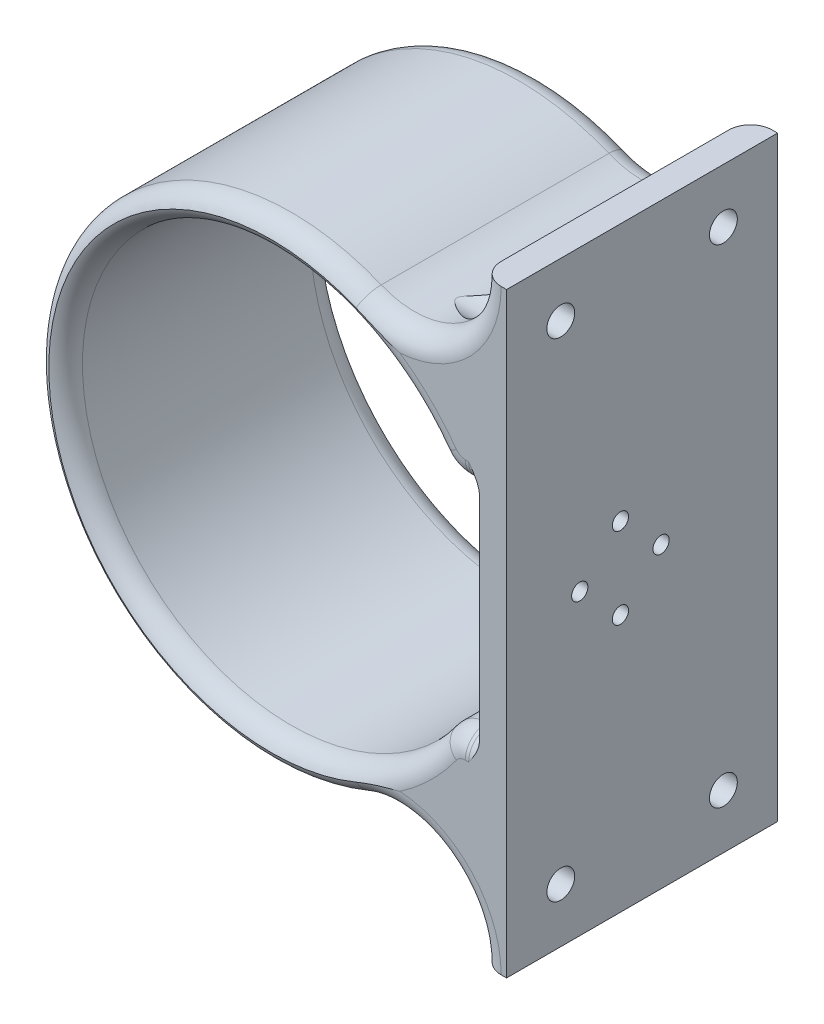
SolidWorks part; units mm, degrees
ref_plane "Front Plane" through (0, 0, 0) normal (0, 0, 1) x (1, 0, 0)
ref_plane "Top Plane" through (0, 0, 0) normal (0, 1, 0) x (1, 0, 0)
ref_plane "Right Plane" through (0, 0, 0) normal (1, 0, 0) x (0, 0, -1)
sketch "Sketch1" plane through (0, 0, 0) normal (0, 0, 1) x (1, 0, 0)
  line L0 (0, 0) -> (55.5625, 0) construction
  line L1 (45.21, 31.75) -> (55.5625, 31.75)
  line L2 (0, 55.245) -> (0, -55.245) construction
  line L3 (55.5625, 31.75) -> (55.5625, -31.75)
  line L4 (55.5625, -31.75) -> (45.21, -31.75)
  line L6 (41.7799, -25.4) -> (49.2125, -25.4)
  line L7 (49.2125, -25.4) -> (49.2125, 25.4)
  line L8 (49.2125, 25.4) -> (41.7799, 25.4)
  line L10 (55.5625, -69.85) -> (49.2125, -69.85)
  line L11 (55.5625, -69.85) -> (55.5625, 69.85)
  line L12 (55.5625, 69.85) -> (49.2125, 69.85)
  line L13 (49.2125, -69.85) -> (49.2125, 69.85)
  line L14 (55.5625, -69.85) -> (49.2125, 69.85) construction
  line L15 (55.5625, 69.85) -> (49.2125, -69.85) construction
  arc A0 (45.21, 31.75) -> (45.21, -31.75) centre (0, 0) ccw
  arc A1 (41.7799, 25.4) -> (41.7799, -25.4) centre (0, 0) ccw
  circle A8 centre (0, 0) radius 48.895 construction
  circle A9 centre (0, 0) radius 55.245 construction
  point P1 (52.3875, 0)
  point P4 (46.1513, 14.1099)
  point P24 (40.0787, 12.2533)
  dimension "D1" = 110.49
  dimension "D4" = 6.35
  dimension "D3" = 6.35
  dimension "D5" = 6.35
  dimension "D6" = 63.5
  dimension "D7" = 55.5625
  dimension "D8" = 38.1
  dimension "D2" = 6.35
extrude "Boss-Extrude1" add sketch "Sketch1" along normal blind 63.5 contours A0 | A1 A0 | L13 L10 L11 L4 | L13 L1 L11 L12 | L13 L4 L3 L1 L7 region at (47.2113, 30.2295, 0) region at (52.3875, 50.8, 0) region at (52.3875, 0, 0) region at (52.3875, -50.8, 0)
sketch3d "3DSketch1" plane through (0, 0, 0) normal (0, 0, 1) x (1, 0, 0)
  dimension "D1" = 71.12
ref_plane "Plane1" through (0, 50.8, 0) normal (0, 1, 0) x (1, 0, 0)
fillet "Fillet1" radius 33.02 2 edges at (45.21, 31.75, 31.75) (45.21, -31.75, 31.75)
fillet "Fillet2" radius 7.62 2 edges at (41.7799, 25.4, 31.75) (41.7799, -25.4, 31.75)
sketch "Sketch2" plane through (49.2125, 0, 0) normal (-1, 0, 0) x (0, 0, 1)
  line L4 (0, 25.4) -> (0, -25.4)
  line L5 (0, -25.4) -> (63.5, -25.4)
  line L6 (63.5, -25.4) -> (63.5, 25.4)
  line L7 (63.5, 25.4) -> (0, 25.4)
  line L8 (0, 25.4) -> (0, -25.4)
  line L9 (0, -25.4) -> (63.5, -25.4)
  line L10 (63.5, -25.4) -> (63.5, 25.4)
  line L11 (63.5, 25.4) -> (0, 25.4)
  circle A0 centre (20.7415, 1.3266) radius 1.5502 construction
  circle A1 centre (30.3045, 10.7631) radius 1.5502 construction
  circle A2 centre (39.7411, 1.2001) radius 1.5502 construction
  circle A3 centre (30.1781, -8.2365) radius 1.5502 construction
  circle A4 centre (20.7415, 1.3266) radius 1.5502
  circle A5 centre (30.3045, 10.7631) radius 1.5502
  circle A6 centre (39.7411, 1.2001) radius 1.5502
  circle A7 centre (30.1781, -8.2365) radius 1.5502
  dimension "D1" = 0
fillet "Fillet3" radius 20.32 2 edges at (49.2125, 31.75, 31.75) (49.2125, -31.75, 31.75)
sketch "Sketch3" plane through (55.5625, 0, 0) normal (1, 0, 0) x (0, 0, -1)
  line L0 (-63.5, -57.15) -> (0, -57.15) construction
  line L1 (-63.5, 69.85) -> (-63.5, -69.85) construction
  line L2 (0, 69.85) -> (0, -69.85) construction
  line L3 (-63.5, -69.85) -> (0, -69.85) construction
  line L5 (34.925, 0) -> (-34.925, 0) construction
  line L6 (-63.5, 57.15) -> (0, 57.15) construction
  circle A0 centre (-50.8, -57.15) radius 3.2639
  circle A1 centre (-31.75, -57.15) radius 3.2639 construction
  circle A2 centre (-12.7, -57.15) radius 3.2639
  circle A3 centre (-12.7, 57.15) radius 3.2639
  circle A4 centre (-31.75, 57.15) radius 3.2639 construction
  circle A5 centre (-50.8, 57.15) radius 3.2639
  circle A6 centre (-50.8, -57.15) radius 3.5179
  circle A7 centre (-31.75, -57.15) radius 3.5179 construction
  circle A8 centre (-12.7, -57.15) radius 3.5179
  circle A9 centre (-50.8, 57.15) radius 3.5179
  circle A10 centre (-31.75, 57.15) radius 3.5179 construction
  circle A11 centre (-12.7, 57.15) radius 3.5179
  point P6 (-31.75, -57.15)
  dimension "D3" = 6.5278
  dimension "D1" = 12.7
  dimension "D2" = 19.05
  dimension "D4" = 19.05
  dimension "D5" = 0.254
extrude "Cut-Extrude1" cut sketch "Sketch3" against normal blind 33.02 contours A2 | A0 | A4 | A3 | A1 | A5 region at (55.5625, -57.15, 50.8) region at (55.5625, -57.15, 12.7) region at (55.5625, 57.15, 12.7)
fillet "Fillet4" radius 5.08 10 edges at (47.5389, 25.4, 0) (42.3912, 26.2381, 0) (47.5389, -25.4, 0) (42.3912, -26.2381, 0) (49.2125, 69.8366, 0) (40.1847, 52.9299, 0) (49.2125, -69.8366, 0) (40.1847, -52.9299, 0) (-48.895, 0, 0) (-55.245, 0, 0)
fillet "Fillet5" radius 5.08 10 edges at (47.5389, 25.4, 63.5) (42.3912, 26.2381, 63.5) (47.5389, -25.4, 63.5) (42.3912, -26.2381, 63.5) (49.2125, 69.8366, 63.5) (40.1847, 52.9299, 63.5) (49.2125, -69.8366, 63.5) (40.1847, -52.9299, 63.5) (-48.895, 0, 63.5) (-55.245, 0, 63.5)
fillet "Fillet6" radius 2.54 6 edges at (49.2125, 26.8879, 62.0121) (49.2125, 26.8879, 1.4879) (49.2125, -26.8879, 62.0121) (49.2125, -26.8879, 1.4879) (49.2125, 25.4, 31.75) (49.2125, -25.4, 31.75)
sketch "Sketch6" plane through (55.5625, 0, 0) normal (1, 0, 0) x (0, 0, -1)
  line L0 (-63.5, 0) -> (0, 0) construction
  line L1 (-63.5, 69.85) -> (-63.5, -69.85) construction
  line L2 (0, 69.85) -> (0, -69.85) construction
  circle A0 centre (-36.83, 0) radius 9.525 construction
  circle A1 centre (-46.355, 0) radius 1.905
  circle A2 centre (-36.83, 9.525) radius 1.905
  circle A3 centre (-27.305, 0) radius 1.905
  circle A4 centre (-36.83, -9.525) radius 1.905
  point P19 (-36.83, 0)
  dimension "D1" = 19.05
  dimension "D2" = 3.81
  dimension "D4" = 26.67
  dimension "D3" = 4
extrude "Cut-Extrude2" cut sketch "Sketch6" against normal up to surface (104.4575 mm away) up to face at (-4.6069, 0, 31.75)
ref_plane "Plane2" through (49.2125, 0, 0) normal (1, 0, 0) x (0, 0, -1)
sketch "Sketch8" plane through (49.2125, 0, 0) normal (1, 0, 0) x (0, 0, -1)
  circle A0 centre (-12.7, -57.15) radius 3.2639 construction
  circle A2 centre (-50.8, -57.15) radius 3.2639 construction
  circle A3 centre (-12.7, 57.15) radius 3.2639 construction
  circle A5 centre (-50.8, 57.15) radius 3.2639 construction
  circle A6 centre (-12.7, -57.15) radius 3.2639
  circle A8 centre (-50.8, -57.15) radius 3.2639
  circle A9 centre (-12.7, 57.15) radius 3.2639
  circle A10 centre (-31.75, 57.15) radius 3.2639
  circle A11 centre (-50.8, 57.15) radius 3.2639
  circle A12 centre (-50.8, 57.15) radius 7.5184
  circle A14 centre (-12.7, 57.15) radius 7.5184
  circle A15 centre (-50.8, -57.15) radius 7.5184
  circle A17 centre (-12.7, -57.15) radius 7.5184
  dimension "D1" = 4.2545
extrude "Cut-Extrude3" cut sketch "Sketch8" against normal blind 20.32 contours A12 A11 | A14 A9 | A17 A6 | A15 A8 region at (49.2125, 57.15, 58.1057) region at (49.2125, 57.15, 20.0057) region at (49.2125, -57.15, 58.1057) region at (49.2125, -57.15, 20.0057)
equation "\"3.5inn\"=3.75"
